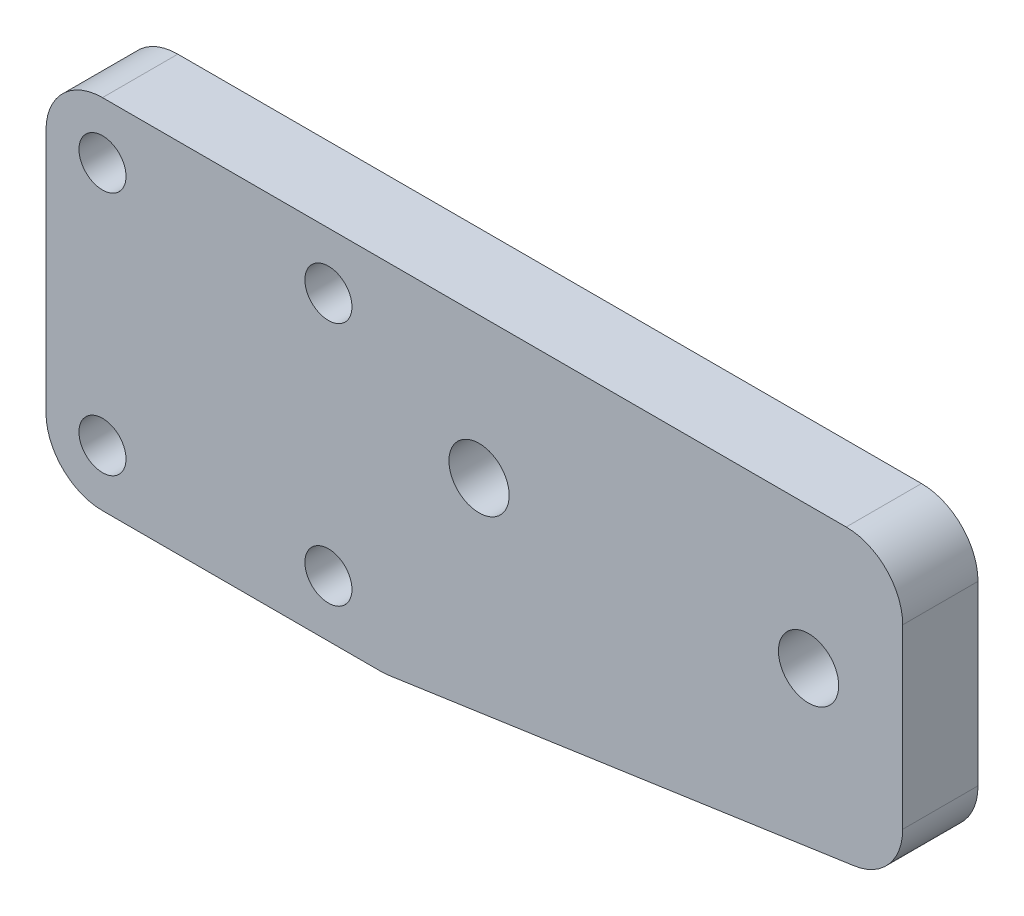
SolidWorks part; units mm, degrees
ref_plane "Plano frontal" through (0, 0, 0) normal (0, 0, 1) x (1, 0, 0)
ref_plane "Plano superior" through (0, 0, 0) normal (0, 1, 0) x (1, 0, 0)
ref_plane "Plano direito" through (0, 0, 0) normal (1, 0, 0) x (0, 0, -1)
sketch "Esboço1" plane through (0, 0, 0) normal (0, 0, 1) x (1, 0, 0)
  line L0 (0, 11.75) -> (0, 0) construction
  line L1 (-9, 9.5) -> (9, 9.5)
  line L2 (-9, 9.5) -> (-9, -9.5)
  line L3 (-9, -9.5) -> (9, -9.5)
  line L4 (9, 9.5) -> (9, -9.5) construction
  line L5 (-9, 9.5) -> (9, -9.5) construction
  line L6 (-9, -9.5) -> (9, 9.5) construction
  line L7 (0, 0) -> (7.3285, 0) construction
  line L8 (9, 9.5) -> (36.5, 9.5)
  line L9 (36.5, 9.5) -> (36.5, -5.5)
  line L10 (36.5, -5.5) -> (9, -9.5)
  line L11 (36.5, 2) -> (13.2423, 2) construction
  line L12 (22.75, 9.5) -> (22.75, -2.0211) construction
  circle A0 centre (6, -6.5) radius 1.25
  circle A1 centre (6, 6.5) radius 1.25
  circle A2 centre (-6, -6.5) radius 1.25
  circle A3 centre (-6, 6.5) radius 1.25
  circle A4 centre (-6, 6.5) radius 3 construction
  circle A5 centre (31.5, 2) radius 1.6
  circle A6 centre (14, 2) radius 1.6
  point P0 (0, 0)
  point P28 (0, 0)
  dimension "D1" = 2.5
  dimension "D4" = 6
  dimension "D7" = 3.2
  dimension "D2" = 13
  dimension "D3" = 12
  dimension "D5" = 27.5
  dimension "D6" = 15
  dimension "D8" = 5
extrude "Ressalto-extrusão1" add sketch "Esboço1" along normal blind 4
fillet "Filete1" radius 3 5 edges at (9, -9.5, 2) (36.5, -5.5, 2) (36.5, 9.5, 2) (-9, -9.5, 2) (-9, 9.5, 2)
